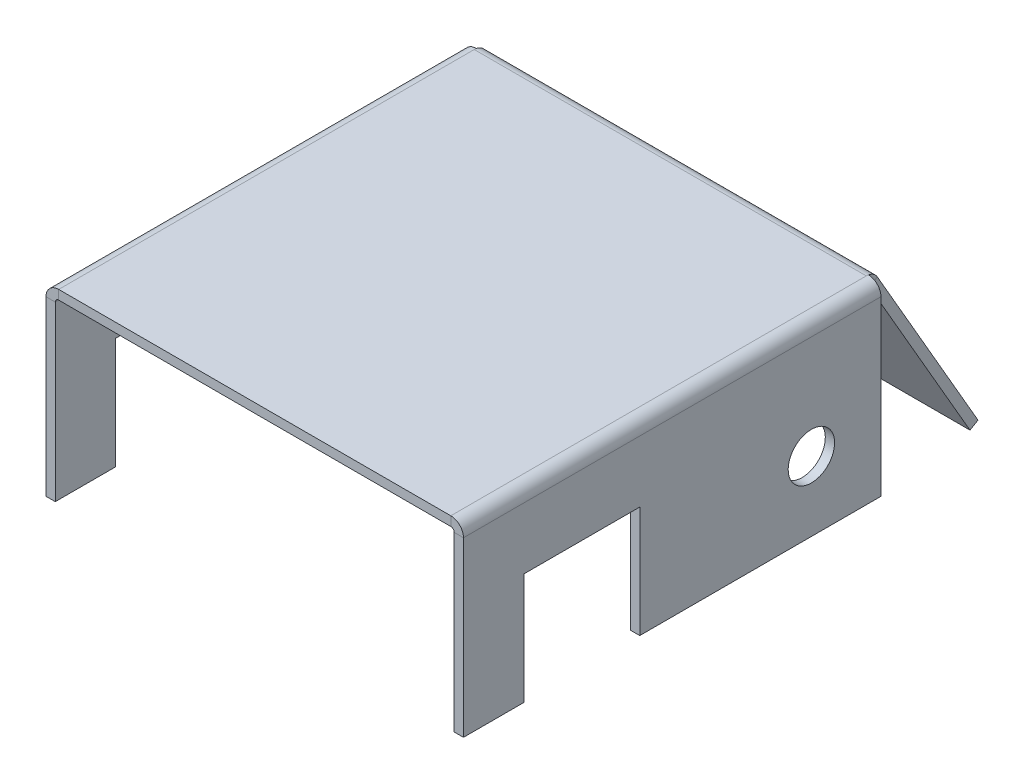
SolidWorks part; units mm, degrees
note: The reader was unsure of these and kept them because the rebuilt part matched: flange length of "Edge-Flange1", "Edge-Flange3", "Edge-Flange5".
ref_plane "Front Plane" through (0, 0, 0) normal (0, 0, 1) x (1, 0, 0)
ref_plane "Top Plane" through (0, 0, 0) normal (0, 1, 0) x (1, 0, 0)
ref_plane "Right Plane" through (0, 0, 0) normal (1, 0, 0) x (0, 0, -1)
sketch "Sketch1" plane through (0, 0, 0) normal (0, 1, 0) x (1, 0, 0)
  line L1 (47.6803, 43.0251) -> (-42.3197, 43.0251)
  line L2 (47.6803, 43.0251) -> (47.6803, -46.9749)
  line L3 (47.6803, -46.9749) -> (-42.3197, -46.9749)
  line L4 (-42.3197, 43.0251) -> (-42.3197, -46.9749)
  dimension "D1" = 90
  dimension "D2" = 90
base flange "Base-Flange1" sketch "Sketch1" thickness 2 reverse thickness direction no parameters "D1"=0.7366
edge flange "Edge-Flange1" sketch "Sketch9" flange angle 90 flange length 40 flange position material inside bend radius 0.7366 thickness 2 parameters "D6"=10
sketch "Sketch9" plane through (-42.3197, -2, 0) normal (-1, 0, 0) x (0, 0, -1)
  line L0 (43.0251, 0) -> (-46.9749, 0) construction
  line L1 (43.0251, 0) -> (-46.9749, 0)
  line L2 (-46.9749, 0) -> (-46.9749, 38)
  line L3 (-46.9749, 38) -> (43.0251, 38)
  line L4 (43.0251, 38) -> (43.0251, 0)
bend "EdgeBend1" bend radius 0.7366 bend angle 90 parameters "D5"=1
edge flange "Edge-Flange3" sketch "Sketch15" flange angle 90 flange length 40 flange position material inside bend radius 0.7366 thickness 2 parameters "D6"=10
sketch "Sketch15" plane through (47.6803, -2, 0) normal (1, 0, 0) x (0, 0, 1)
  line L0 (46.9749, 0) -> (-43.0251, 0) construction
  line L1 (46.9749, 0) -> (-43.0251, 0)
  line L2 (-43.0251, 0) -> (-43.0251, 38)
  line L3 (-43.0251, 38) -> (46.9749, 38)
  line L4 (46.9749, 38) -> (46.9749, 0)
bend "EdgeBend3" bend radius 0.7366 bend angle 90 parameters "D5"=2
edge flange "Edge-Flange5" sketch "Sketch21" flange angle 120 flange length 45 flange position material outside bend radius 0.7366 thickness 2 parameters "D6"=10
sketch "Sketch21" plane through (0, -2, -43.0251) normal (0, -0.5, 0.866) x (-1, 0, 0)
  line L1 (39.5831, 0) -> (-44.9437, 0) construction
  line L2 (-44.9437, 0) -> (-44.9437, 43.8453)
  line L3 (-44.9437, 43.8453) -> (39.5831, 43.8453)
  line L4 (39.5831, 43.8453) -> (39.5831, 0)
  line L5 (39.5831, 0) -> (-44.9437, 0)
bend "EdgeBend5" bend radius 0.7366 bend angle 60 parameters "D5"=3
sketch "Sketch25" plane through (47.6803, 0, 0) normal (1, 0, 0) x (0, 0, -1)
  line L0 (-46.9749, -40) -> (43.0251, -40) construction
  line L1 (-33.9749, -16) -> (-8.9749, -16)
  line L2 (-33.9749, -16) -> (-33.9749, -40)
  line L3 (-33.9749, -40) -> (-8.9749, -40)
  line L4 (-8.9749, -16) -> (-8.9749, -40)
  dimension "D1" = 25
  dimension "D2" = 24
  dimension "D3" = 13
extrude "Cut-Extrude1" cut sketch "Sketch25" against normal through all
sketch "Sketch26" plane through (-42.3197, 0, 0) normal (-1, 0, 0) x (0, 0, 1)
  line L0 (-43.0251, -2.7366) -> (-43.0251, -40) construction
  line L1 (-43.0251, -40) -> (8.9749, -40) construction
  circle A0 centre (-28.0251, -25) radius 5
  dimension "D1" = 15
  dimension "D2" = 15
extrude "Cut-Extrude2" cut sketch "Sketch26" against normal through all contours A0
sketch "Bend-Lines1" [suppressed] plane through (0, 0, 0) normal (0, 1, 0) x (1, 0, 0)
sketch "Bounding-Box1" [suppressed] plane through (0, 0, 0) normal (0, 1, 0) x (1, 0, 0)
sheet metal parameters "Sheet-Metal1" thickness 2 parameters "D1"=0.7366
flat pattern "Flat-Pattern1" [suppressed]
sketch "Bend-Lines2" plane through (0, 0, 0) normal (0, 1, 0) x (1, 0, 0)
sketch3d "Bounding-Box2" [suppressed]
  line L0 (-47.6803, 43.0251, 0) -> (42.3197, 43.0251, 0) construction
  line L1 (-47.6803, -46.9749, 0) -> (42.3197, -46.9749, 0) construction
  line L2 (-47.6803, 43.0251, 0) -> (-47.6803, -46.9749, 0) construction
  line L3 (42.3197, 43.0251, 0) -> (42.3197, -46.9749, 0) construction
sheet metal parameters "Sheet-Metal2" thickness 2 parameters "D1"=0.7366
flat pattern "Flat-Pattern1"
sketch "Bend-Lines2" plane through (0, 0, 0) normal (0, 1, 0) x (1, 0, 0)
  line L0 (-40.9471, 43.0251) -> (-40.9471, -46.9749) construction
  line L1 (-40.9471, 43.0251) -> (-40.9471, -46.9749) construction
sketch3d "Bounding-Box2" [suppressed]
  line L0 (47.6803, 43.0251, 0) -> (-79.5744, 43.0251, 0) construction
  line L1 (47.6803, -46.9749, 0) -> (-79.5744, -46.9749, 0) construction
  line L2 (47.6803, 43.0251, 0) -> (47.6803, -46.9749, 0) construction
  line L3 (-79.5744, 43.0251, 0) -> (-79.5744, -46.9749, 0) construction
bend of the flat pattern "Flatten-<EdgeBend1>1"
sheet metal parameters "Sheet-Metal4" thickness 2 parameters "D1"=0.7366
flat pattern "Flat-Pattern1"
sketch "Bend-Lines2" plane through (0, 0, 0) normal (0, 1, 0) x (1, 0, 0)
  line L0 (-40.9471, 43.0251) -> (-40.9471, -46.9749) construction
  line L1 (-40.9471, 43.0251) -> (-40.9471, -46.9749) construction
  line L2 (46.3076, -46.9749) -> (46.3076, 43.0251) construction
  line L3 (46.3076, -46.9749) -> (46.3076, 43.0251) construction
sketch3d "Bounding-Box2" [suppressed]
  line L0 (84.9349, 43.0251, 0) -> (-79.5744, 43.0251, 0) construction
  line L1 (84.9349, -46.9749, 0) -> (-79.5744, -46.9749, 0) construction
  line L2 (84.9349, 43.0251, 0) -> (84.9349, -46.9749, 0) construction
  line L3 (-79.5744, 43.0251, 0) -> (-79.5744, -46.9749, 0) construction
bend of the flat pattern "Flatten-<EdgeBend1>1"
bend of the flat pattern "Flatten-<EdgeBend3>1"
sheet metal parameters "Sheet-Metal6" thickness 2 parameters "D1"=0.7366
flat pattern "Flat-Pattern1"
sketch "Bend-Lines2" plane through (0, 0, 0) normal (0, 1, 0) x (1, 0, 0)
  line L0 (-40.9471, 43.0251) -> (-40.9471, -46.9749) construction
  line L1 (-40.9471, 43.0251) -> (-40.9471, -46.9749) construction
  line L2 (46.3076, -46.9749) -> (46.3076, 43.0251) construction
  line L3 (46.3076, -46.9749) -> (46.3076, 43.0251) construction
  line L4 (44.9437, 43.5091) -> (-39.5831, 43.5091) construction
  line L5 (44.9437, 43.5091) -> (-39.5831, 43.5091) construction
sketch3d "Bounding-Box2" [suppressed]
  line L0 (84.9349, 87.8384, 0) -> (-79.5744, 87.8384, 0) construction
  line L1 (84.9349, -46.9749, 0) -> (-79.5744, -46.9749, 0) construction
  line L2 (84.9349, 87.8384, 0) -> (84.9349, -46.9749, 0) construction
  line L3 (-79.5744, 87.8384, 0) -> (-79.5744, -46.9749, 0) construction
bend of the flat pattern "Flatten-<EdgeBend1>1"
bend of the flat pattern "Flatten-<EdgeBend3>1"
bend of the flat pattern "Flatten-<EdgeBend5>1"
sheet metal parameters "Sheet-Metal7" thickness 2 parameters "D1"=0.7366
flat pattern "Flat-Pattern1"
sketch "Bend-Lines2" plane through (0, 0, 0) normal (0, 1, 0) x (1, 0, 0)
  line L0 (-40.9471, 43.0251) -> (-40.9471, -46.9749) construction
  line L1 (-40.9471, 43.0251) -> (-40.9471, -46.9749) construction
  line L2 (46.3076, -46.9749) -> (46.3076, 43.0251) construction
  line L3 (46.3076, -46.9749) -> (46.3076, 43.0251) construction
  line L4 (44.9437, 43.5091) -> (-39.5831, 43.5091) construction
  line L5 (44.9437, 43.5091) -> (-39.5831, 43.5091) construction
sketch3d "Bounding-Box2" [suppressed]
  line L0 (84.9349, 87.8384, 0) -> (-79.5744, 87.8384, 0) construction
  line L1 (84.9349, -46.9749, 0) -> (-79.5744, -46.9749, 0) construction
  line L2 (84.9349, 87.8384, 0) -> (84.9349, -46.9749, 0) construction
  line L3 (-79.5744, 87.8384, 0) -> (-79.5744, -46.9749, 0) construction
bend of the flat pattern "Flatten-<EdgeBend1>1"
bend of the flat pattern "Flatten-<EdgeBend3>1"
bend of the flat pattern "Flatten-<EdgeBend5>1"
sheet metal parameters "Sheet-Metal8" thickness 2 parameters "D1"=0.7366
flat pattern "Flat-Pattern1"
sketch "Bend-Lines2" plane through (0, 0, 0) normal (0, 1, 0) x (1, 0, 0)
  line L0 (-40.9471, 43.0251) -> (-40.9471, -46.9749) construction
  line L1 (-40.9471, 43.0251) -> (-40.9471, -46.9749) construction
  line L2 (46.3076, -46.9749) -> (46.3076, 43.0251) construction
  line L3 (46.3076, -46.9749) -> (46.3076, 43.0251) construction
  line L4 (44.9437, 43.5091) -> (-39.5831, 43.5091) construction
  line L5 (44.9437, 43.5091) -> (-39.5831, 43.5091) construction
sketch3d "Bounding-Box2" [suppressed]
  line L0 (84.9349, 87.8384, 0) -> (-79.5744, 87.8384, 0) construction
  line L1 (84.9349, -46.9749, 0) -> (-79.5744, -46.9749, 0) construction
  line L2 (84.9349, 87.8384, 0) -> (84.9349, -46.9749, 0) construction
  line L3 (-79.5744, 87.8384, 0) -> (-79.5744, -46.9749, 0) construction
bend of the flat pattern "Flatten-<EdgeBend1>1"
bend of the flat pattern "Flatten-<EdgeBend3>1"
bend of the flat pattern "Flatten-<EdgeBend5>1"
